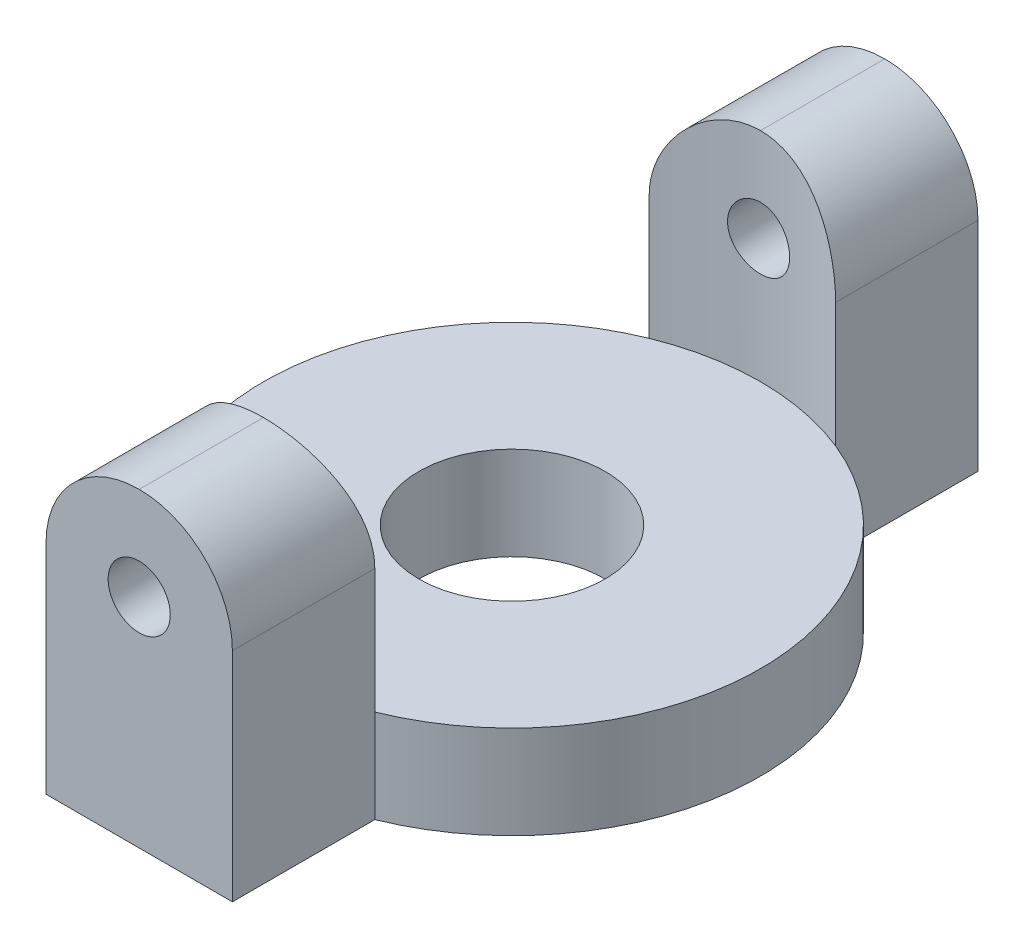
SolidWorks part; units mm, degrees
ref_plane "Front Plane" through (0, 0, 0) normal (0, 0, 1) x (1, 0, 0)
ref_plane "Top Plane" through (0, 0, 0) normal (0, 1, 0) x (1, 0, 0)
ref_plane "Right Plane" through (0, 0, 0) normal (1, 0, 0) x (0, 0, -1)
sketch "Sketch1" plane through (0, 0, 0) normal (0, 1, 0) x (1, 0, 0)
  circle A0 centre (0, 0) radius 4
  circle A1 centre (0, 0) radius 1.5
extrude "Boss-Extrude1" add sketch "Sketch1" along normal blind 1.5
sketch "Sketch2" plane through (0, 1.5, 0) normal (0, 1, 0) x (1, 0, 0)
  line L1 (3.1754, 0) -> (1.5877, 2.75)
  line L2 (1.5877, 2.75) -> (-1.5877, 2.75)
  line L3 (-1.5877, 2.75) -> (-3.1754, 0)
  line L4 (-3.1754, 0) -> (-1.5877, -2.75)
  line L5 (-1.5877, -2.75) -> (1.5877, -2.75)
  line L6 (1.5877, -2.75) -> (3.1754, 0)
  circle A0 centre (0, 0) radius 2.75 construction
  dimension "D1" = 5.5
sketch "Sketch3" plane through (0, 0, 0) normal (0, 1, 0) x (1, 0, 0)
  line L0 (-1.5, -3.7081) -> (-1.5, -6)
  line L1 (-1.5, 6) -> (1.5, 6)
  line L2 (-1.5, 6) -> (-1.5, 3.7081)
  line L3 (-1.5, -6) -> (1.5, -6)
  line L4 (1.5, 6) -> (1.5, 3.7081)
  line L5 (-1.5, 6) -> (1.5, -6) construction
  line L6 (-1.5, -6) -> (1.5, 6) construction
  line L7 (1.5, -3.7081) -> (1.5, -6)
  circle A0 centre (0, 0) radius 4 construction
  arc A1 (-1.5, 3.7081) -> (1.5, 3.7081) centre (0, 0) cw
  arc A2 (-1.5, -3.7081) -> (1.5, -3.7081) centre (0, 0) ccw
  point P0 (0, 0)
  dimension "D1" = 6
  dimension "D2" = 3
extrude "Boss-Extrude2" add sketch "Sketch3" along normal blind 5
sketch "Sketch4" plane through (0, 0, 6) normal (0, 0, 1) x (1, 0, 0)
  line L0 (-1.5, 5) -> (1.5, 5) construction
  line L1 (-1.5, 5) -> (-1.5, 0) construction
  circle A0 centre (0, 3.5) radius 0.5
  dimension "D1" = 1
  dimension "D2" = 1.5
  dimension "D3" = 1.5
extrude "Cut-Extrude1" cut sketch "Sketch4" against normal through all
fillet "Fillet1" radius 1.5 4 edges at (1.5, 5, 4.854) (-1.5, 5, 4.854) (1.5, 5, -4.854) (-1.5, 5, -4.854)
